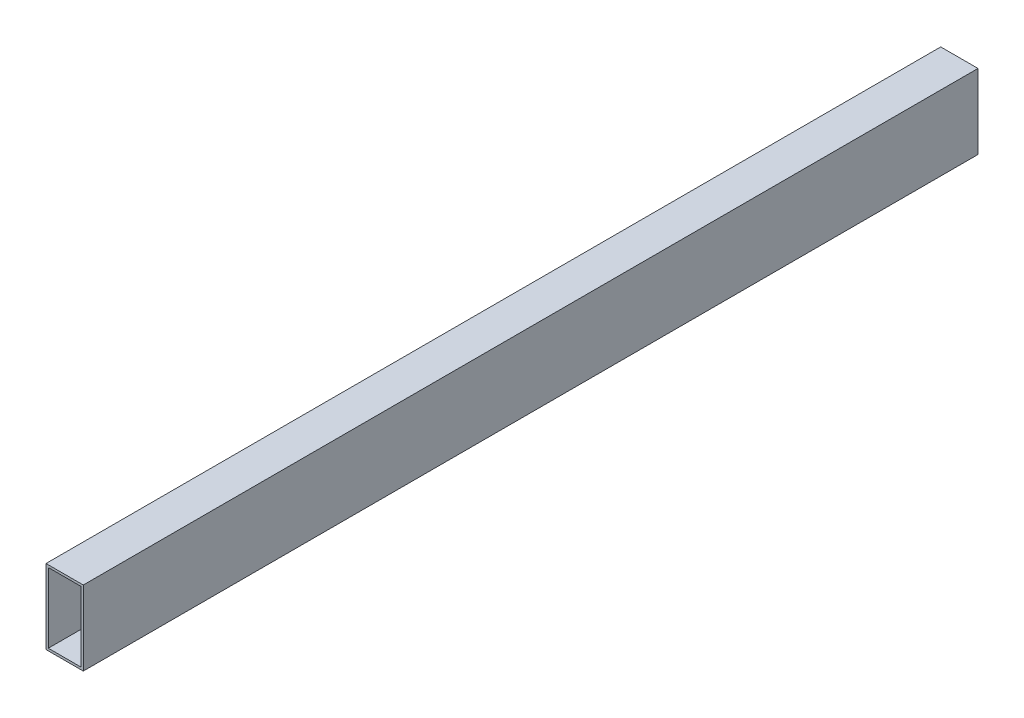
SolidWorks part; units mm, degrees
material "6061-T4 (SS)"
ref_plane "Front Plane" through (0, 0, 0) normal (0, 0, 1) x (1, 0, 0)
ref_plane "Top Plane" through (0, 0, 0) normal (0, 1, 0) x (1, 0, 0)
ref_plane "Right Plane" through (0, 0, 0) normal (1, 0, 0) x (0, 0, -1)
sketch "Sketch1" plane through (0, 0, 0) normal (0, 0, 1) x (1, 0, 0)
  line L0 (1.5875, 49.2125) -> (23.8125, 49.2125)
  line L5 (0, 0) -> (25.4, 0)
  line L6 (0, 0) -> (0, 50.8)
  line L7 (0, 50.8) -> (25.4, 50.8)
  line L8 (25.4, 0) -> (25.4, 50.8)
  line L13 (23.8125, 1.5875) -> (23.8125, 49.2125)
  line L14 (1.5875, 1.5875) -> (23.8125, 1.5875)
  line L15 (1.5875, 1.5875) -> (1.5875, 49.2125)
  dimension "D1" = 25.4
  dimension "D2" = 1.5875
  dimension "D3" = 50.8
extrude "Boss-Extrude1" add sketch "Sketch1" along normal blind 609.6
sketch "Sketch2" plane through (0, 0, 0) normal (-1, 0, 0) x (0, 0, 1)
  line L0 (609.6, 50.8) -> (609.6, 0) construction
  line L1 (609.6, 50.8) -> (0, 50.8) construction
  circle A16 centre (558.8, 38.1) radius 2.4892
  circle A17 centre (533.4, 38.1) radius 2.4892
  circle A18 centre (508, 38.1) radius 2.4892
  circle A19 centre (482.6, 38.1) radius 2.4892
  circle A21 centre (558.8, 12.7) radius 2.4892
  circle A22 centre (533.4, 12.7) radius 2.4892
  circle A23 centre (508, 12.7) radius 2.4892
  circle A24 centre (482.6, 12.7) radius 2.4892
  circle A26 centre (584.2, 12.7) radius 2.4892
  circle A29 centre (584.2, 38.1) radius 2.4892
  circle A30 centre (457.2, 38.1) radius 2.4892 [skipped]
  circle A31 centre (457.2, 12.7) radius 2.4892 [skipped]
  point P2 (477.0367, 35.0526)
  point P30 (565.6546, 20.7441)
  point P31 (0, 0)
  dimension "D4" = 25.4
  dimension "D5" = 6
  dimension "D6" = 2
  dimension "D1" = 4.9784
  dimension "D7" = 12.7
  dimension "D2" = 25.4
  dimension "D3" = 25.4
extrude "Cut-Extrude1" cut sketch "Sketch2" against normal up to next
